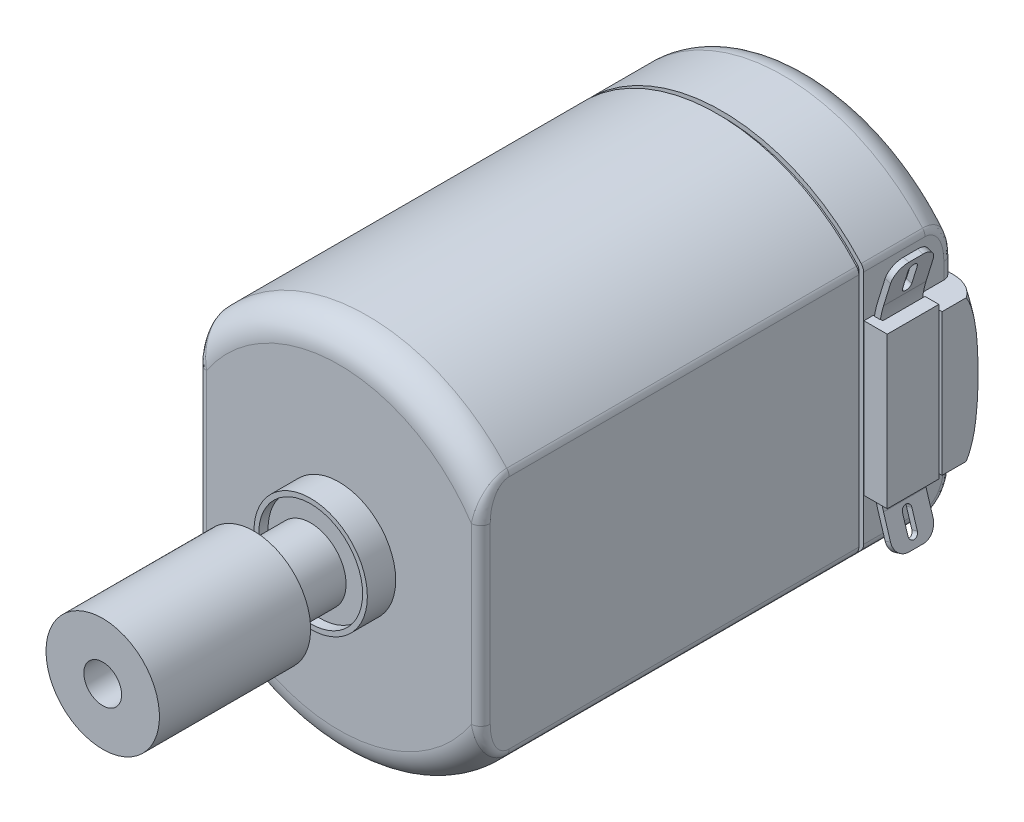
SolidWorks part; units mm, degrees
ref_plane "Front Plane" through (0, 0, 0) normal (0, 0, 1) x (1, 0, 0)
ref_plane "Top Plane" through (0, 0, 0) normal (0, 1, 0) x (1, 0, 0)
ref_plane "Right Plane" through (0, 0, 0) normal (1, 0, 0) x (0, 0, -1)
ref_plane "Plane1" through (0, 0, 5) normal (0, 0, 1) x (1, 0, 0)
sketch "Sketch1" plane through (0, 0, 0) normal (0, 0, 1) x (1, 0, 0)
  line L1 (0, 9.875) -> (0, -9.875) construction
  circle A2 centre (0, 0) radius 9.875
extrude "Boss-Extrude1" add sketch "Sketch1" along normal blind 25
fillet "Fillet1" radius 1.5 2 edges at (9.875, 0, 0) (9.875, 0, 25)
sketch "Sketch2" plane through (0, 0, 0) normal (0, 0, 1) x (1, 0, 0)
  line L1 (-7.5, 12.7478) -> (7.5, 12.7478)
  line L3 (-7.5, -12.2522) -> (7.5, -12.2522)
  line L4 (7.5, 12.7478) -> (7.5, 3.75)
  line L5 (-18.8727, 16.8375) -> (14.6421, 16.8375)
  line L6 (-18.8727, 16.8375) -> (-18.8727, -25.1353)
  line L7 (-18.8727, -25.1353) -> (14.6421, -25.1353)
  line L8 (14.6421, 16.8375) -> (14.6421, -25.1353)
  line L11 (-7.5, 12.7478) -> (-7.5, -12.2522)
  line L12 (8.9, 3.75) -> (7.5, 3.75)
  line L14 (7.5, -3.75) -> (8.9, -3.75)
  line L15 (8.9, -3.75) -> (8.9, 3.75)
  line L16 (7.5, -3.75) -> (7.5, -12.2522)
  dimension "D1" = 25
  dimension "D2" = 15
  dimension "D4" = 7.5
  dimension "D7" = 1.4
extrude "Cut-Extrude2" cut sketch "Sketch2" along normal blind 30
sketch "Sketch8" plane through (8.9, 0, 0) normal (-1, 0, 0) x (0, 0, 1)
  line L1 (2, 4.5419) -> (26.0252, 4.5419)
  line L2 (2, 4.5419) -> (2, -4.6354)
  line L3 (2, -4.6354) -> (26.0252, -4.6354)
  line L4 (26.0252, 4.5419) -> (26.0252, -4.6354)
  line L5 (0, 3.727) -> (0, -3.727) construction
  dimension "D1" = 2
extrude "Cut-Extrude3" cut sketch "Sketch8" along normal up to surface (1.4 mm away) up to face at (7.5, -0.4184, 12.611)
sketch "Sketch3" plane through (0, 0, 0) normal (0, 0, -1) x (-1, 0, 0)
  line L0 (-4.9749, -0.5) -> (-3.9749, -0.5)
  line L2 (-3.9749, 0.5) -> (-4.9749, 0.5)
  line L6 (-2.1249, 3) -> (-2.8749, 3)
  line L7 (-2.1249, 3) -> (-2.1249, -2.5)
  line L8 (0, 0) -> (0, 7.9436) construction
  line L9 (-2.1249, -2.5) -> (-2.8749, -2.5)
  line L10 (-2.8749, 3) -> (-2.8749, -2.5)
  line L14 (3.75, 3.3072) -> (3.75, -3.3072)
  arc A3 (-3.9749, 0.5) -> (-3.9749, -0.5) centre (-3.9749, 0) cw
  arc A4 (-4.9749, 0.5) -> (3.75, 3.3072) centre (0, 0) cw
  arc A5 (3.75, -3.3072) -> (-4.9749, -0.5) centre (0, 0) cw
  dimension "D1" = 0.75
  dimension "D5" = 5
  dimension "D9" = 3
  dimension "D3" = 0.5
  dimension "D7" = 5
  dimension "D2" = 2.8749
  dimension "D4" = 1
  dimension "D6" = 3.75
  dimension "D8" = 3.3072
  dimension "D10" = 5.5
extrude "Boss-Extrude2" add sketch "Sketch3" along normal blind 2.25
sketch "Sketch4" plane through (0, 0, -2.25) normal (0, 0, -1) x (-1, 0, 0)
  circle A0 centre (0, 0) radius 1
extrude "Boss-Extrude3" add sketch "Sketch4" along normal blind 0.6
fillet "Fillet2" radius 0.1 1 edges at (-1, 0, -2.85)
fillet "Fillet3" radius 0.25 5 edges at (1.5314, -4.7597, -2.25) (1.5314, 4.7597, -2.25) (-3.75, -3.3072, -1.125) (-3.75, 3.3072, -1.125) (-3.75, 0, -2.25)
sketch "Sketch5" plane through (0, 0, 25) normal (0, 0, 1) x (1, 0, 0)
  circle A0 centre (0, 0) radius 3
  circle A1 centre (0, 0) radius 2.75
  dimension "D1" = 6
  dimension "D2" = 0.25
extrude "Boss-Extrude4" add sketch "Sketch5" along normal blind 1.5
sketch "Sketch6" plane through (0, 0, 25) normal (0, 0, 1) x (1, 0, 0)
  circle A1 centre (0, 0) radius 2.75
  circle A2 centre (0, 0) radius 2.75
  dimension "D1" = 0
extrude "Boss-Extrude5" add sketch "Sketch6" along normal blind 1
sketch "Sketch7" plane through (0, 0, 26) normal (0, 0, 1) x (1, 0, 0)
  circle A0 centre (0, 0) radius 1
extrude "Boss-Extrude6" add sketch "Sketch7" along normal blind 8.5
fillet "Fillet4" radius 0.25 1 edges at (1, 0, 34.5)
sketch "Sketch9" plane through (0, 0, 0) normal (1, 0, 0) x (0, 0, -1)
  line L0 (-26.5, 1) -> (-26.5, 1.875)
  line L1 (-26.5, 2.75) -> (-26.5, -2.75) construction
  line L2 (-26.5, 1.875) -> (-29.5, 1.875)
  line L3 (-29.5, 1.875) -> (-29.5, 1)
  line L6 (-29.5, 1) -> (-26.5, 1)
  line L7 (-27.1023, 0) -> (-37.2814, 0) construction
  dimension "D1" = 1
  dimension "D3" = 3
  dimension "D4" = 1.875
revolve "Revolve1" add sketch "Sketch9" angle 360 about L7
fillet "Fillet5" radius 0.5 15 edges at (-7.5, 6.2343, 0.907) (-7.5, 0, 0) (-7.5, -6.0098, 0.6499) (-7.5, -6.4238, 12.5) (-7.5, -6.2343, 24.093) (-7.5, 0, 25) (-7.5, 6.0098, 24.3501) (7.5, 6.1892, 2.1559) (7.5, -6.4238, 12.5) (7.5, 5.6583, 22.4002) (7.5, 0, 25) (7.5, -6.1892, 22.8441) (7.5, -5.6583, 2.5998) (-7.5, 6.4238, 12.5) (7.5, 6.4238, 12.5)
sketch "Sketch11" plane through (0, 0, 5) normal (0, 0, 1) x (1, 0, 0)
  line L7 (-9.8679, 10.1979) -> (10.3845, 10.1979)
  line L8 (-9.8679, 10.1979) -> (-9.8679, -11.0381)
  line L9 (-9.8679, -11.0381) -> (10.3845, -11.0381)
  line L10 (10.3845, 10.1979) -> (10.3845, -11.0381)
  line L12 (7.25, 4.5979) -> (7.25, 6.2362)
  line L13 (7.25, -4.5979) -> (7.25, 4.5979)
  line L14 (7.25, -6.2362) -> (7.25, -4.5979)
  line L15 (-7.25, -4.5979) -> (-7.25, -6.2362)
  line L16 (-7.25, 6.2362) -> (-7.25, 4.5979)
  line L17 (-7.25, 4.5979) -> (-7.25, -4.5979)
  line L18 (7.25, 4.5979) -> (7.25, 6.2362)
  line L19 (7.25, -4.5979) -> (7.25, 4.5979)
  line L20 (7.25, -6.2362) -> (7.25, -4.5979)
  line L21 (-7.25, -4.5979) -> (-7.25, -6.2362)
  line L22 (-7.25, 6.2362) -> (-7.25, 4.5979)
  line L23 (-7.25, 4.5979) -> (-7.25, -4.5979)
  arc A12 (7.25, 6.2362) -> (7.1867, 6.4025) centre (7, 6.2362) ccw
  arc A13 (7.1867, -6.4025) -> (7.25, -6.2362) centre (7, -6.2362) ccw
  arc A14 (-7.1867, -6.4025) -> (7.1867, -6.4025) centre (0, 0) ccw
  arc A15 (-7.25, -6.2362) -> (-7.1867, -6.4025) centre (-7, -6.2362) ccw
  arc A16 (7.1867, 6.4025) -> (-7.1867, 6.4025) centre (0, 0) ccw
  arc A17 (-7.1867, 6.4025) -> (-7.25, 6.2362) centre (-7, 6.2362) ccw
  arc A18 (7.25, 6.2362) -> (7.1867, 6.4025) centre (7, 6.2362) ccw
  arc A19 (7.1867, -6.4025) -> (7.25, -6.2362) centre (7, -6.2362) ccw
  arc A20 (-7.1867, -6.4025) -> (7.1867, -6.4025) centre (0, 0) ccw
  arc A21 (-7.25, -6.2362) -> (-7.1867, -6.4025) centre (-7, -6.2362) ccw
  arc A22 (7.1867, 6.4025) -> (-7.1867, 6.4025) centre (0, 0) ccw
  arc A23 (-7.1867, 6.4025) -> (-7.25, 6.2362) centre (-7, 6.2362) ccw
  dimension "D1" = 0.25
extrude "Cut-Extrude5" cut sketch "Sketch11" against normal blind 0.25
sketch "Sketch12" plane through (0, 0, 0) normal (0, 1, 0) x (1, 0, 0)
  line L0 (8.7316, -2) -> (8.7316, -4.7295)
  line L1 (8.7316, -4.7295) -> (7.5, -4.7295)
  line L2 (7.5, -4.7295) -> (7.5, -4.2295)
  line L3 (7.5, -1.5) -> (7.5, -4.75) construction
  line L4 (7.5, -4.2295) -> (8, -4.2295)
  line L5 (8, -4.2295) -> (8, -2)
  line L6 (8.9, -2) -> (7.5, -2) construction
  line L7 (8, -2) -> (8.7316, -2)
  dimension "D1" = 0.5
  dimension "D2" = 0.5
extrude "Boss-Extrude7" add sketch "Sketch12" along normal mid plane 8
sketch "Sketch13" plane through (0, 0, 2) normal (0, 0, 1) x (1, 0, 0)
  line L0 (0, 0) -> (15.0354, 0) construction
  line L1 (7.5177, -3.2453) -> (7.5177, 3.2453)
  line L2 (7.5, 4) -> (8.7316, 4) construction
  line L3 (7.7405, 4.7211) -> (8.3605, 6.7283)
  line L4 (8.3605, 6.7283) -> (8.6485, 6.6393)
  line L5 (8.6485, 6.6393) -> (8.056, 4.7211)
  line L6 (7.8332, 3.2453) -> (7.8332, -3.2453)
  line L7 (8.6485, -6.6393) -> (8.056, -4.7211)
  line L8 (8.3605, -6.7283) -> (8.6485, -6.6393)
  line L9 (7.7405, -4.7211) -> (8.3605, -6.7283)
  arc A0 (7.5177, 3.2453) -> (7.7405, 4.7211) centre (12.5177, 3.2453) cw
  arc A1 (8.056, 4.7211) -> (7.8332, 3.2453) centre (12.8332, 3.2453) ccw
  arc A2 (8.056, -4.7211) -> (7.8332, -3.2453) centre (12.8332, -3.2453) cw
  arc A3 (7.5177, -3.2453) -> (7.7405, -4.7211) centre (12.5177, -3.2453) ccw
  point P13 (7.5177, 4)
  point P16 (7.8332, 4)
  point P23 (7.8332, 0)
  point P25 (7.5177, 0)
  dimension "D1" = 5
extrude "Boss-Extrude8" add sketch "Sketch13" along normal blind 2.25
fillet "Fillet6" radius 0.75 4 edges at (8.5045, -6.6838, 4.25) (8.5045, -6.6838, 2) (8.5045, 6.6838, 2) (8.5045, 6.6838, 4.25)
sketch "Sketch14" plane through (6.0228, -1.8606, 0) normal (0.9554, -0.2952, 0) x (0, 0, -1)
  line L0 (-3.125, 8.3029) -> (-3.125, 7.319) construction
  line L1 (-2.8786, 8.3029) -> (-2.8786, 7.319)
  line L2 (-3.3714, 8.3029) -> (-3.3714, 7.319)
  arc A0 (-2.8786, 8.3029) -> (-3.3714, 8.3029) centre (-3.125, 8.3029) ccw
  arc A1 (-3.3714, 7.319) -> (-2.8786, 7.319) centre (-3.125, 7.319) ccw
  point P2 (-3.125, 7.811)
extrude "Cut-Extrude6" cut sketch "Sketch14" against normal blind 0.5
mirror "Mirror2" about plane through (0, 0, 0) normal (0, 1, 0) of "Cut-Extrude6"
sketch "Sketch15" [suppressed] plane through (0, 0, 0) normal (0, 0, -1) x (-1, 0, 0)
  line L0 (-1.625, 9.5137) -> (-1.625, 11.6685)
  line L1 (-1.625, 11.6685) -> (1.625, 11.6685)
  line L2 (1.625, 11.6685) -> (1.625, 9.5137)
  line L3 (0, 0) -> (14.9283, 0) construction
  line L4 (1.625, -11.6685) -> (1.625, -9.5137)
  line L5 (-1.625, -11.6685) -> (1.625, -11.6685)
  line L6 (-1.625, -9.5137) -> (-1.625, -11.6685)
  arc A0 (-1.625, 9.5137) -> (1.625, 9.5137) centre (0, 9.5137) ccw
  arc A1 (-1.625, -9.5137) -> (1.625, -9.5137) centre (0, -9.5137) cw
extrude "Cut-Extrude7" [suppressed] cut sketch "Sketch15" against normal blind 6
fillet "Fillet7" [suppressed] radius 0.75
sketch "Sketch16" plane through (0, 0, 0) normal (0, 1, 0) x (1, 0, 0)
  line L0 (-1, -29.5) -> (-1, -34.25) construction
  line L1 (-1, -29.5) -> (-3, -29.5)
  line L2 (-1, -29.5) -> (-1, -37.5)
  line L3 (-1, -37.5) -> (-3, -37.5)
  line L4 (-3, -29.5) -> (-3, -37.5)
  line L5 (-1.875, -29.5) -> (1.875, -29.5) construction
  line L7 (0, -29.3946) -> (0, -35.2588)
  dimension "D1" = 2
  dimension "D2" = 8
  dimension "D3" = 0
revolve "Revolve2" add sketch "Sketch16" angle 360 about L7 region at (-2, 0, 33.5)
